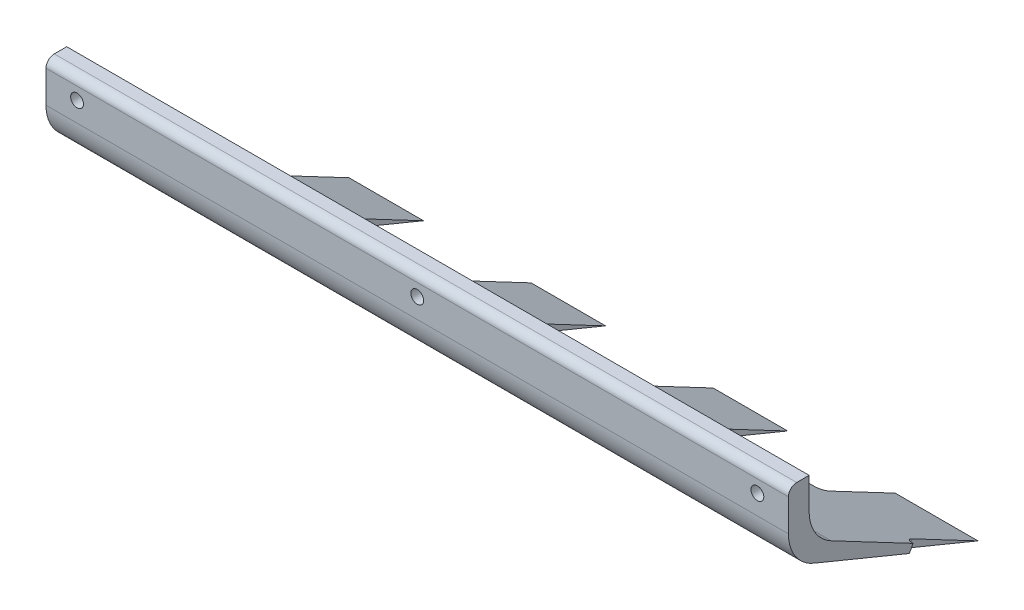
SolidWorks part; units mm, degrees
other "Markup1"
sketch "Sketch9" plane through (179.4, -40.9075, -59.0885) normal (0.9903, -0.01, -0.1384) x (-0.1383, 0.0097, -0.9903)
material "TPU"
ref_plane "Front Plane" through (0, 0, 0) normal (0, 0, 1) x (1, 0, 0)
ref_plane "Top Plane" through (0, 0, 0) normal (0, 1, 0) x (1, 0, 0)
ref_plane "Right Plane" through (0, 0, 0) normal (1, 0, 0) x (0, 0, -1)
sketch "Sketch1" plane through (0, 0, 0) normal (1, 0, 0) x (0, 0, -1)
  line L0 (0, -15.4886) -> (0, -30.4886) construction
  line L1 (0, -30.4886) -> (45.3154, -51.6195) construction
  line L2 (-2.5, -15.4886) -> (-2.5, -31.932)
  line L3 (2.5, -15.4886) -> (2.5, -29.0453)
  line L4 (-2.5, -15.4886) -> (2.5, -15.4886)
  line L8 (2.5, -29.0453) -> (45.3154, -51.6195)
  line L9 (-2.5, -15.4886) -> (-2.5, -30.4886) construction
  line L10 (-2.5, -31.932) -> (45.3154, -51.6195)
  line L11 (2.5, -15.4886) -> (2.5, -30.4886) construction
  dimension "D1" = 2.5
  dimension "D3" = 15
  dimension "D4" = 115
  dimension "D5" = 50
  dimension "D2" = 2.5
extrude "Boss-Extrude1" add sketch "Sketch1" along normal blind 179.4
fillet "Fillet3" radius 10 2 edges at (89.7, -29.0453, -2.5) (89.7, -31.932, 2.5)
sketch "Sketch4" plane through (0, 0, -2.5) normal (0, 0, -1) x (-1, 0, 0)
  line L0 (-179.4, -15.4886) -> (0, -15.4886) construction
  line L1 (-179.4, -23.0129) -> (-179.4, -15.4886) construction
  line L2 (-89.7, -15.4886) -> (-89.7, -73.3062) construction
  line L3 (-179.4, -15.4886) -> (0, -15.4886) construction
  circle A0 centre (-171.9, -20.4886) radius 1.55
  circle A1 centre (-7.5, -20.4886) radius 1.55
  circle A2 centre (-89.7, -20.4886) radius 1.55
  point P16 (0, 0)
  point P17 (0, 0)
  dimension "D1" = 5
  dimension "D2" = 7.5
  dimension "D3" = 3.1
  dimension "D4" = 3.1
extrude "Cut-Extrude3" cut sketch "Sketch4" against normal up to next
sketch "Sketch7" plane through (0, -21.6959, 11.4391) normal (0, 0.8846, -0.4664) x (1, 0, 0)
  line L1 (157.4, 64.1599) -> (131.4, 64.1599)
  line L2 (157.4, 64.1599) -> (157.4, 44.1599)
  line L3 (157.4, 44.1599) -> (131.4, 44.1599)
  line L4 (131.4, 64.1599) -> (131.4, 44.1599)
  line L5 (179.4, 64.1599) -> (179.4, 21.7903) construction
  line L6 (179.4, 42.9751) -> (-3.7579, 42.9751) construction
  line L7 (113.4, 64.1599) -> (113.4, 44.1599)
  line L8 (113.4, 64.1599) -> (87.4, 64.1599)
  line L9 (87.4, 64.1599) -> (87.4, 44.1599)
  line L10 (113.4, 44.1599) -> (87.4, 44.1599)
  line L11 (69.4, 64.1599) -> (69.4, 44.1599)
  line L12 (69.4, 64.1599) -> (43.4, 64.1599)
  line L13 (43.4, 64.1599) -> (43.4, 44.1599)
  line L14 (69.4, 44.1599) -> (43.4, 44.1599)
  line L15 (25.4, 64.1599) -> (25.4, 44.1599)
  line L16 (25.4, 64.1599) -> (0, 64.1599)
  line L18 (25.4, 44.1599) -> (0, 44.1599)
  line L20 (179.4, 64.1599) -> (177.4, 64.1599)
  line L21 (179.4, 64.1599) -> (179.4, 44.1599)
  line L22 (179.4, 44.1599) -> (177.4, 44.1599)
  line L23 (177.4, 64.1599) -> (177.4, 44.1599)
  line L25 (0, 64.1599) -> (0, 44.1599)
  line L28 (179.4, 64.1599) -> (90.9834, 64.1599) construction
  dimension "D1" = 26
  dimension "D2" = 20
  dimension "D3" = 22
  dimension "D5" = 2
  dimension "D6" = 20
  dimension "D7" = 18
extrude "Cut-Extrude5" cut sketch "Sketch7" against normal up to next
fillet "Fillet6" radius 2 8 edges at (25.4, -43.1312, -27.1812) (43.4, -43.1312, -27.1812) (69.4, -43.1312, -27.1812) (87.4, -43.1312, -27.1812) (113.4, -43.1312, -27.1812) (177.4, -43.1312, -27.1812) (131.4, -43.1312, -27.1812) (157.4, -43.1312, -27.1812)
fillet "Fillet7" radius 2 1 edges at (89.7, -15.4886, 2.5)
